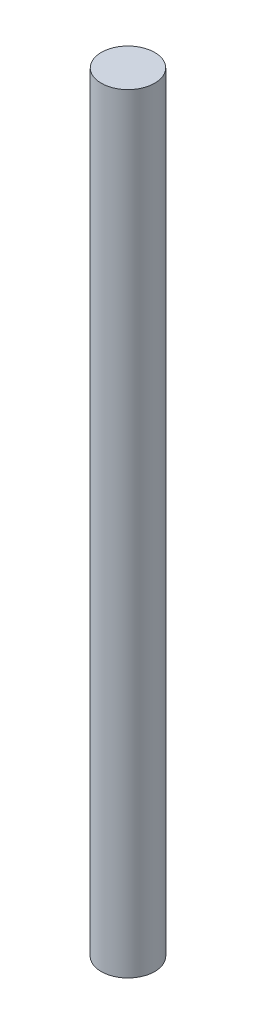
SolidWorks part; units mm, degrees
material "Plain Carbon Steel"
ref_plane "Front Plane" through (0, 0, 0) normal (0, 0, 1) x (1, 0, 0)
ref_plane "Top Plane" through (0, 0, 0) normal (0, 1, 0) x (1, 0, 0)
ref_plane "Right Plane" through (0, 0, 0) normal (1, 0, 0) x (0, 0, -1)
sketch "Sketch1" plane through (0, 0, 0) normal (0, 1, 0) x (1, 0, 0)
  circle A0 centre (0, 0) radius 3.9688
extrude "Boss-Extrude1" add sketch "Sketch1" along normal blind 114.3
